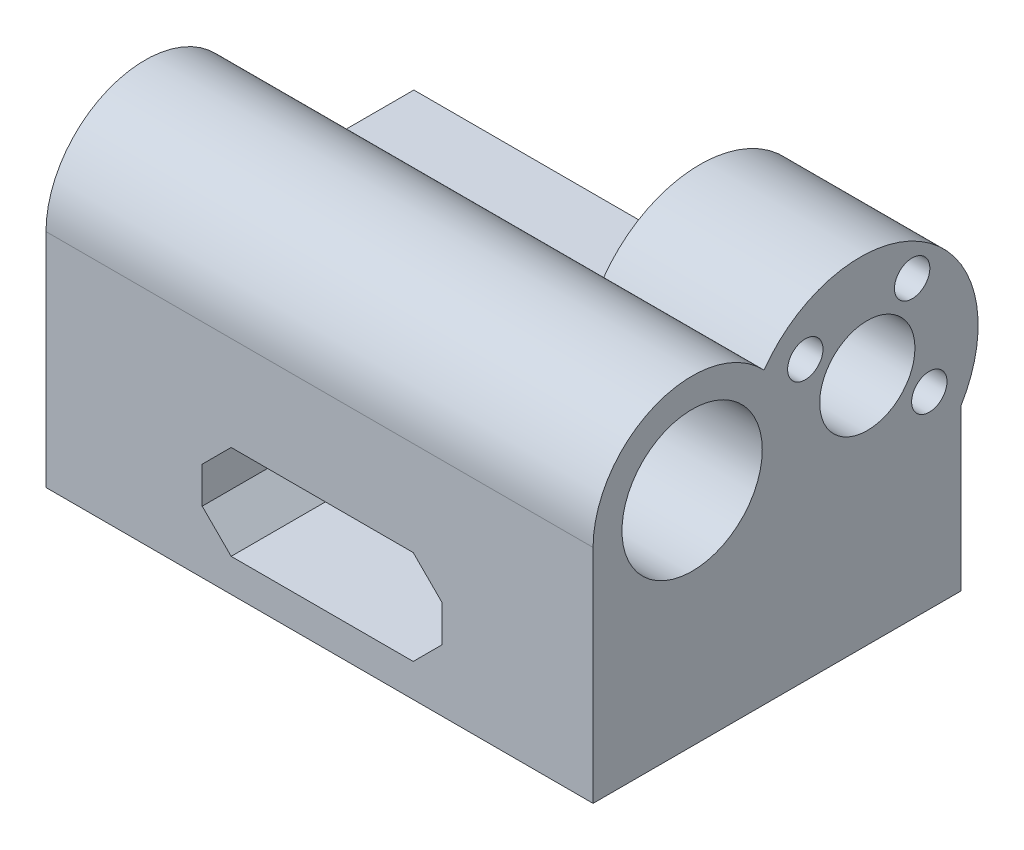
SolidWorks part; units mm, degrees
ref_plane "Front Plane" through (0, 0, 0) normal (0, 0, 1) x (1, 0, 0)
ref_plane "Top Plane" through (0, 0, 0) normal (0, 1, 0) x (1, 0, 0)
ref_plane "Right Plane" through (0, 0, 0) normal (1, 0, 0) x (0, 0, -1)
sketch "Sketch2" plane through (0, 0, 0) normal (0, 1, 0) x (1, 0, 0)
  line L1 (-29, -19.5) -> (29, -19.5)
  line L2 (-29, -19.5) -> (-29, 19.5)
  line L3 (-29, 19.5) -> (29, 19.5)
  line L4 (29, -19.5) -> (29, 19.5)
  line L5 (-29, -19.5) -> (29, 19.5) construction
  line L6 (-29, 19.5) -> (29, -19.5) construction
  point P0 (0, 0)
  dimension "D1" = 58
  dimension "D2" = 39
extrude "Boss-Extrude1" add sketch "Sketch2" along normal blind 17
sketch "Sketch3" plane through (29, 0, 0) normal (1, 0, 0) x (0, 0, -1)
  line L0 (-19.5, 0) -> (19.5, 0) construction
  line L2 (-19.5, 17) -> (-19.5, 0) construction
  line L4 (-19.5, 23.5) -> (-19.5, 17)
  line L5 (1.5, 23.5) -> (1.5, 17)
  line L6 (-19.5, 17) -> (19.5, 17) construction
  line L7 (-19.5, 17) -> (1.5, 17)
  arc A0 (1.5, 23.5) -> (-19.5, 23.5) centre (-9, 23.5) ccw
  dimension "D2" = 21
  dimension "D4" = 23.5
  dimension "D5" = 10.5
extrude "Boss-Extrude2" add sketch "Sketch3" against normal up to surface (58 mm away) up to face at (-29, 8.5, 0)
sketch "Sketch4" plane through (29, 0, 0) normal (1, 0, 0) x (0, 0, -1)
  line L0 (-19.5, 0) -> (19.5, 0) construction
  circle A0 centre (8.8229, 23.5) radius 12.5
  dimension "D1" = 25
  dimension "D2" = 23.5
extrude "Boss-Extrude3" add sketch "Sketch4" against normal blind 17
sketch "Sketch5" plane through (0, 0, -19.5) normal (0, 0, -1) x (-1, 0, 0)
  line L0 (-13, 6.57) -> (-13, 10.427)
  line L1 (-13, 10.427) -> (-9.93, 13.497)
  line L2 (-9.93, 13.497) -> (9.37, 13.497)
  line L3 (9.37, 13.497) -> (12.44, 10.427)
  line L4 (12.44, 10.427) -> (12.44, 6.57)
  line L5 (12.44, 6.57) -> (9.37, 3.5)
  line L6 (9.37, 3.5) -> (-9.93, 3.5)
  line L7 (-9.93, 3.5) -> (-13, 6.57)
  line L8 (-29, 0) -> (29, 0) construction
  line L9 (-29, 17) -> (-29, 0) construction
  dimension "D1" = 3.857
  dimension "D2" = 3.857
  dimension "D3" = 135
  dimension "D4" = 135
  dimension "D5" = 3.07
  dimension "D6" = 3.07
  dimension "D7" = 3.07
  dimension "D8" = 3.07
  dimension "D9" = 19.3
  dimension "D10" = 3.5
  dimension "D11" = 16
extrude "Cut-Extrude1" cut sketch "Sketch5" against normal through all
sketch "Sketch6" plane through (0, 0, -19.5) normal (0, 0, -1) x (-1, 0, 0)
  line L0 (-29, 0) -> (29, 0) construction
  line L1 (-29, 17) -> (-29, 0) construction
  circle A0 centre (-23, 8.5) radius 4.076
  circle A1 centre (22, 8.5) radius 4.076
  dimension "D5" = 8.152
  dimension "D6" = 8.152
  dimension "D1" = 8.5
  dimension "D2" = 8.5
  dimension "D3" = 6
  dimension "D4" = 51
extrude "Cut-Extrude2" cut sketch "Sketch6" against normal blind 23
sketch "Sketch7" plane through (29, 0, 0) normal (1, 0, 0) x (0, 0, -1)
  line L0 (8.8229, 23.5) -> (8.8229, 24.75) construction
  line L1 (8.8229, 24.75) -> (9.5729, 24.75) construction
  circle A0 centre (-9, 23.5) radius 7.4365
  circle A1 centre (9.5729, 24.75) radius 5.05
  dimension "D1" = 10.1
  dimension "D2" = 14.873
  dimension "D3" = 1.25
  dimension "D4" = 0.75
extrude "Cut-Extrude3" cut sketch "Sketch7" against normal through all
sketch "Sketch8" plane through (29, 0, 0) normal (1, 0, 0) x (0, 0, -1)
  line L0 (9.5729, 24.75) -> (2.9997, 29.5258) construction
  line L1 (9.5729, 24.75) -> (5.1826, 18.7072) construction
  line L2 (9.5729, 24.75) -> (16.1462, 19.9742) construction
  line L3 (9.5729, 24.75) -> (14.3278, 31.2946) construction
  line L4 (2.9997, 29.5258) -> (4.5166, 28.4237) construction
  line L5 (16.1462, 19.9742) -> (14.6293, 21.0763) construction
  line L6 (19.5, 17) -> (1.5, 17) construction
  line L7 (14.3278, 31.2946) -> (13.2258, 29.7777) construction
  circle A1 centre (2.9997, 29.5258) radius 1.875
  circle A2 centre (14.3278, 31.2946) radius 1.875
  circle A3 centre (16.1462, 19.9742) radius 1.875
  point P0 (3.1161, 29.6886)
  dimension "D1" = 3.75
  dimension "D2" = 54
  dimension "D3" = 3.75
  dimension "D4" = 3.75
  dimension "D5" = 12.5
  dimension "D6" = 6.25
extrude "Cut-Extrude4" cut sketch "Sketch8" against normal through all
sketch "Sketch9" plane through (12, 0, 0) normal (-1, 0, 0) x (0, 0, 1)
  circle A0 centre (-2.9997, 29.5258) radius 2.75
  circle A1 centre (-16.1462, 19.9742) radius 2.75
  dimension "D1" = 5.5
  dimension "D2" = 5.5
